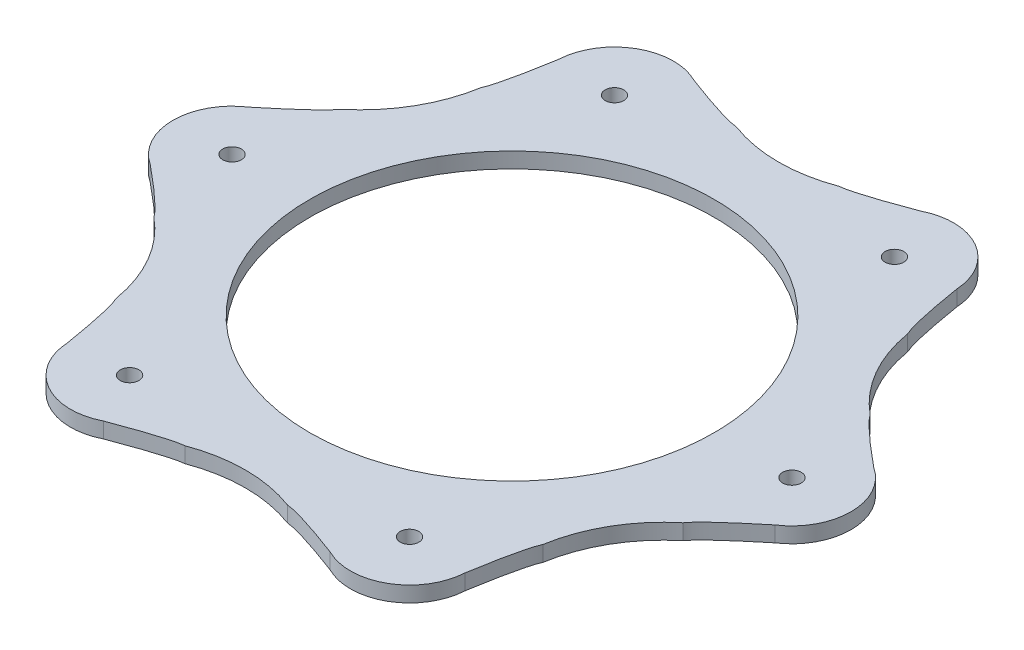
SolidWorks part; units mm, degrees
material "ABS"
ref_plane "Front" through (0, 0, 0) normal (0, 0, 1) x (1, 0, 0)
ref_plane "Top" through (0, 0, 0) normal (0, 1, 0) x (1, 0, 0)
ref_plane "Right" through (0, 0, 0) normal (1, 0, 0) x (0, 0, -1)
sketch "Sketch1" plane through (0, 0, 0) normal (0, 1, 0) x (1, 0, 0)
  line L0 (0, 45) -> (0, -45) construction
  line L1 (-45, 0) -> (45, 0) construction
  line L10 (0, 45) -> (0, 37.5) construction
  circle A0 centre (0, 0) radius 45
  circle A1 centre (0, 0) radius 32.5
  dimension "D6" = 90
  dimension "D1" = 65
extrude "Boss-Extrude2" add sketch "Sketch1" along normal blind 2.5
ref_plane "Plane1" through (0, 2.5, 0) normal (0, 1, 0) x (1, 0, 0)
sketch "Sketch2" plane through (0, 2.5, 0) normal (0, 1, 0) x (1, 0, 0)
  line L0 (0, 45) -> (0, -45) construction
  line L1 (-45, 0) -> (45, 0) construction
  line L2 (-54.5, 0) -> (-35.5, 0) construction
  line L4 (-51.7175, -6.7175) -> (-45, 0) construction
  circle A0 centre (0, 0) radius 45 construction
  arc A2 (-42.2345, 15.532) -> (-42.2345, -15.532) centre (0, 0) ccw
  arc A3 (-50.2124, 7.9424) -> (-50.2124, -7.9424) centre (-45, 0) ccw
  spline S0 degree 3 poles (-50.2124, -7.9424) (-45.316, -11.9596) (-42.6567, -14.4895) (-42.2345, -15.532) knots 0.089312 0.089312 0.089312 0.089312 1 1 1 1
  spline S1 degree 3 poles (-50.2124, 7.9424) (-45.316, 11.9596) (-42.6567, 14.4895) (-42.2345, 15.532) knots 0.089312 0.089312 0.089312 0.089312 1 1 1 1
  dimension "D2" = 45
extrude "Boss-Extrude4" add sketch "Sketch2" against normal up to surface (2.5 mm away) up to face at (0, 0, 45)
pattern_circular "CirPattern1" count 6 over 360 about axis through (0, 2.5, 0) along (0, 1, 0) of "Boss-Extrude4"
ref_plane "Plane2" through (0, 2.5, 0) normal (0, 1, 0) x (1, 0, 0)
sketch "Sketch5" plane through (0, 2.5, 0) normal (0, 1, 0) x (1, 0, 0)
  line L0 (0, 45) -> (0, -45) construction
  line L1 (-8.2247, 44.3422) -> (0, 46.6578)
  line L2 (0, 46.6578) -> (8.2247, 44.3422)
  line L3 (40.4069, 23.3289) -> (42.5138, 15.0483)
  line L4 (34.2891, 29.2939) -> (40.4069, 23.3289)
  line L5 (40.4069, -23.3289) -> (34.2891, -29.2939)
  line L6 (42.5138, -15.0483) -> (40.4069, -23.3289)
  line L7 (0, -46.6578) -> (-8.2247, -44.3422)
  line L8 (8.2247, -44.3422) -> (0, -46.6578)
  line L9 (-40.4069, -23.3289) -> (-42.5138, -15.0483)
  line L10 (-34.2891, -29.2939) -> (-40.4069, -23.3289)
  line L11 (-40.4069, 23.3289) -> (-34.2891, 29.2939)
  line L12 (-42.5138, 15.0483) -> (-40.4069, 23.3289)
  arc A0 (7.6662, 44.3422) -> (-7.6662, 44.3422) centre (0, 0) ccw construction
  arc A1 (-7.6662, -44.3422) -> (7.6662, -44.3422) centre (0, 0) ccw construction
  arc A2 (-8.2247, 44.3422) -> (8.2247, 44.3422) centre (0, 66.2885) ccw
  arc A3 (34.2891, 29.2939) -> (42.5138, 15.0483) centre (57.4076, 33.1443) ccw
  arc A4 (42.5138, -15.0483) -> (34.2891, -29.2939) centre (57.4076, -33.1443) ccw
  arc A5 (8.2247, -44.3422) -> (-8.2247, -44.3422) centre (0, -66.2885) ccw
  arc A6 (-34.2891, -29.2939) -> (-42.5138, -15.0483) centre (-57.4076, -33.1443) ccw
  arc A7 (-42.5138, 15.0483) -> (-34.2891, 29.2939) centre (-57.4076, 33.1443) ccw
  parabola Q0 (-7.6662, 44.3422) -> (-18.2279, 47.4564) focus (-7.4049, 44.5798) apex (-7.3043, 44.5299) construction
  parabola Q1 (18.2279, 47.4564) -> (7.6662, 44.3422) focus (7.4049, 44.5798) apex (7.3043, 44.5299) construction
  point P42 (0, 0)
  dimension "D1" = 6
extrude "Cut-Extrude2" cut sketch "Sketch5" against normal blind 2.5
ref_plane "Plane3" through (0, 2.5, 0) normal (0, 1, 0) x (1, 0, 0)
sketch "Sketch6" plane through (0, 2.5, 0) normal (0, 1, 0) x (1, 0, 0)
  line L0 (0, 42.8517) -> (0, -42.8517) construction
  circle A0 centre (-45, 0) radius 1.5
  arc A1 (-8.2247, 44.3422) -> (8.2247, 44.3422) centre (0, 66.2885) ccw construction
  arc A2 (8.2247, -44.3422) -> (-8.2247, -44.3422) centre (0, -66.2885) ccw construction
  circle A7 centre (-22.5, 38.9711) radius 1.5
  circle A8 centre (22.5, 38.9711) radius 1.5
  circle A9 centre (45, 0) radius 1.5
  circle A10 centre (22.5, -38.9711) radius 1.5
  circle A11 centre (-22.5, -38.9711) radius 1.5
  point P37 (0, 0)
  dimension "D4" = 3
  dimension "D5" = 22.5
  dimension "D3" = 6
extrude "Cut-Extrude3" cut sketch "Sketch6" against normal mid plane 10
